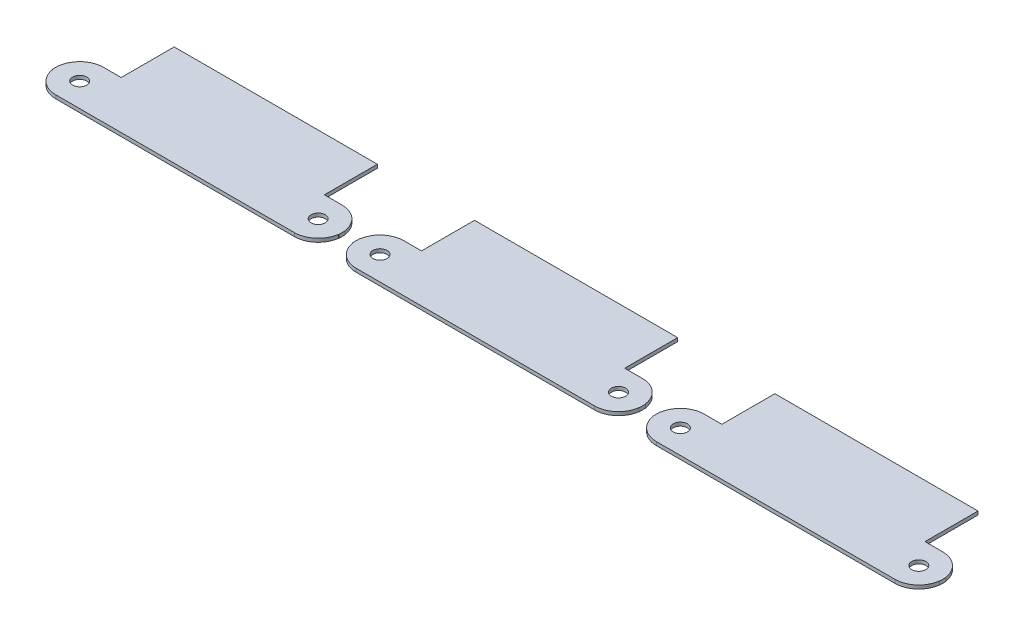
SolidWorks part; units mm, degrees
ref_plane "Front Plane" through (0, 0, 0) normal (0, 0, 1) x (1, 0, 0)
ref_plane "Top Plane" through (0, 0, 0) normal (0, 1, 0) x (1, 0, 0)
ref_plane "Right Plane" through (0, 0, 0) normal (1, 0, 0) x (0, 0, -1)
sketch "Sketch1" plane through (0, 0, 0) normal (0, 1, 0) x (1, 0, 0)
  line L0 (0, 0) -> (67.5, 0) construction
  line L1 (0, 6.75) -> (5, 6.75)
  line L2 (0, 6.75) -> (67.5, 6.75) construction
  line L3 (0, 6.75) -> (0, -6.75) construction
  line L4 (0, -6.75) -> (67.5, -6.75)
  line L5 (67.5, 6.75) -> (67.5, -6.75) construction
  line L6 (0, 6.75) -> (67.5, -6.75) construction
  line L7 (0, -6.75) -> (67.5, 6.75) construction
  line L8 (5, 6.75) -> (5, 21.75)
  line L9 (5, 21.75) -> (62.5, 21.75)
  line L10 (62.5, 21.75) -> (62.5, 6.75)
  line L11 (62.5, 6.75) -> (67.5, 6.75)
  line L12 (33.75, 0) -> (33.75, 21.75) construction
  line L13 (74.1897, 0.9) -> (74.25, 0.9)
  line L14 (74.25, 0.9) -> (74.25, -0.9)
  line L15 (74.25, -0.9) -> (74.1897, -0.9)
  line L17 (67.5, 0) -> (74.25, 0) construction
  line L32 (-6.75, 1) -> (-6.75, -1)
  line L33 (-6.75, -1) -> (-6.6755, -1)
  line L44 (-6.75, 1) -> (-6.6755, 1)
  circle A0 centre (0, 0) radius 2
  circle A1 centre (67.5, 0) radius 2
  arc A2 (0, 6.75) -> (0, -6.75) centre (0, 0) ccw construction
  arc A3 (67.5, -6.75) -> (67.5, 6.75) centre (67.5, 0) ccw construction
  arc A5 (67.5, 6.75) -> (74.1897, 0.9) centre (67.5, 0) cw
  arc A7 (74.1897, -0.9) -> (67.5, -6.75) centre (67.5, 0) cw
  arc A8 (-6.6755, 1) -> (0, 6.75) centre (0, 0) cw
  arc A9 (-6.6755, -1) -> (0, -6.75) centre (0, 0) ccw
  point P5 (33.75, 0)
  point P23 (-6.75, 0)
  dimension "D3" = 15
  dimension "D6" = 4
  dimension "D2" = 13.5
  dimension "D4" = 67.5
  dimension "D5" = 5
  dimension "D13" = 2
extrude "Boss-Extrude1" add sketch "Sketch1" along normal blind 1 contours L4 A3 L11 L10 L9 L8 L1 A2 A0 A1 | L14 L9 | A3 | A2 L44 L32 L33 | L14 region at (33.7497, 0, -6.4966)
pattern_linear "LPattern1" count 3 spacing 85 along (1, 0, 0) of bodies 101
